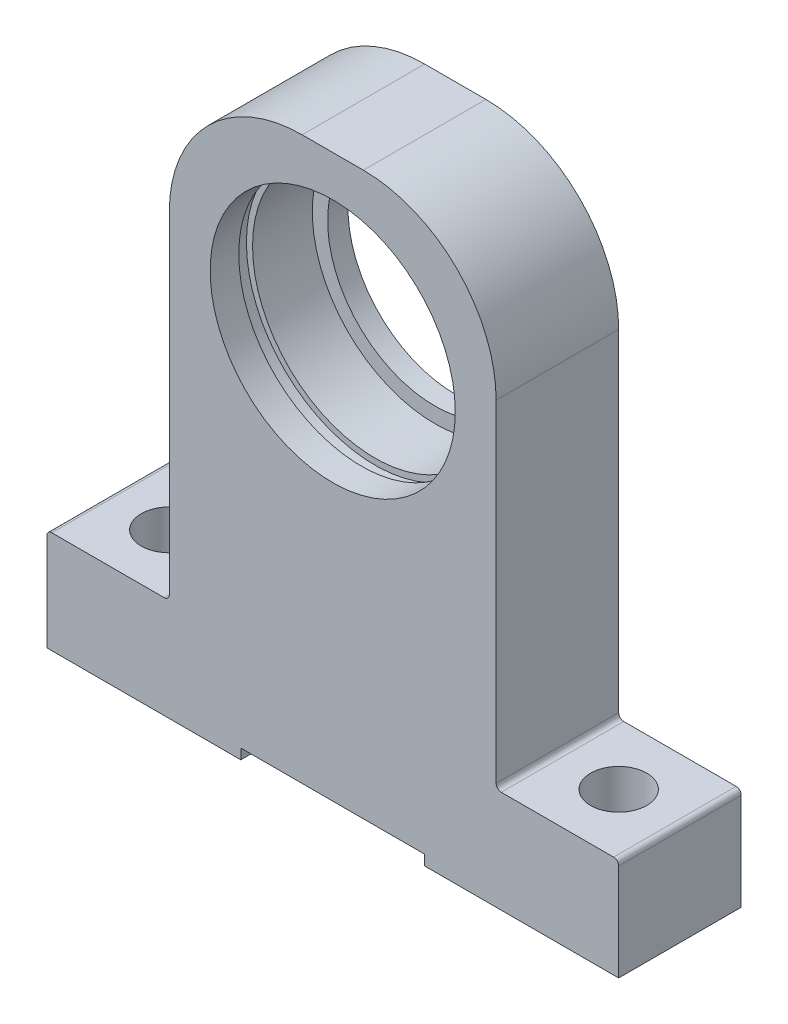
SolidWorks part; units mm, degrees
material "A6063"
ref_plane "Front Plane" through (0, 0, 0) normal (0, 0, 1) x (1, 0, 0)
ref_plane "Top Plane" through (0, 0, 0) normal (0, 1, 0) x (1, 0, 0)
ref_plane "Right Plane" through (0, 0, 0) normal (1, 0, 0) x (0, 0, -1)
ref_axis "Axis_X" through (-88.99, 0, 0) along (1, 0, 0)
ref_axis "Axis_Y" through (0, 55, 0) along (0, -1, 0)
ref_axis "Axis_Z" through (0, 0, -88.99) along (0, 0, 1)
sketch "Sketch1" plane through (0, 0, 0) normal (0, 0, 1) x (1, 0, 0)
  line L0 (-28, -40) -> (28, -40)
  line L1 (28, -40) -> (28, -30)
  line L2 (28, -30) -> (16, -30)
  line L3 (16, -30) -> (16, 16)
  line L4 (16, 16) -> (-16, 16)
  line L5 (-16, 16) -> (-16, -30)
  line L6 (-16, -30) -> (-28, -30)
  line L7 (-28, -30) -> (-28, -40)
  line L8 (0, 16) -> (0, -40) construction
  circle A0 centre (0, 0) radius 10.5
  dimension "DH_s" = 21
  dimension "S" = 10
  dimension "L" = 56
  dimension "L2" = 32
  dimension "H" = 56
  dimension "H_s" = 40
extrude "Boss-Extrude1" add sketch "Sketch1" along normal blind 12
sketch "Sketch2" plane through (0, 0, 0) normal (0, 0, 1) x (1, 0, 0)
  line L0 (3, 16) -> (16, 16)
  line L1 (16, 16) -> (16, 3)
  line L2 (-3, 16) -> (-16, 16)
  line L3 (-16, 16) -> (-16, 3)
  line L4 (16, 16) -> (-16, 16) construction
  line L5 (16, -30) -> (16, 16) construction
  line L7 (-16, 16) -> (-16, -30) construction
  arc A0 (3, 16) -> (16, 3) centre (3, 3) cw
  arc A1 (-16, 3) -> (-3, 16) centre (-3, 3) cw
  dimension "R" = 13
extrude "Cut-Extrude1" cut sketch "Sketch2" along normal through all
sketch "Sketch3" plane through (0, 0, 0) normal (0, 0, 1) x (1, 0, 0)
  line L0 (16, -29.5) -> (16, -30)
  line L1 (16, -30) -> (16, 16) construction
  line L2 (16, -30) -> (16.5, -30)
  line L3 (28, -30) -> (16, -30) construction
  line L4 (-16, -29.5) -> (-16, -30)
  line L5 (-16, 16) -> (-16, -30) construction
  line L6 (-16, -30) -> (-16.5, -30)
  line L7 (-16, -30) -> (-28, -30) construction
  arc A0 (16, -29.5) -> (16.5, -30) centre (16.5, -29.5) ccw
  arc A1 (-16.5, -30) -> (-16, -29.5) centre (-16.5, -29.5) ccw
  dimension "FIX_1" = 0.5
extrude "Boss-Extrude2" add sketch "Sketch3" along normal through all
sketch "Sketch4" plane through (0, 0, 0) normal (0, 0, 1) x (1, 0, 0)
  line L0 (-27.5, -30) -> (-28, -30)
  line L1 (-16, -30) -> (-28, -30) construction
  line L2 (-28, -30) -> (-28, -30.5)
  line L3 (-28, -30) -> (-28, -40) construction
  line L4 (27.5, -30) -> (28, -30)
  line L5 (28, -30) -> (16, -30) construction
  line L6 (28, -30) -> (28, -30.5)
  line L7 (28, -40) -> (28, -30) construction
  arc A0 (-28, -30.5) -> (-27.5, -30) centre (-27.5, -30.5) cw
  arc A1 (27.5, -30) -> (28, -30.5) centre (27.5, -30.5) cw
  dimension "FIX_2" = 0.5
extrude "Cut-Extrude2" cut sketch "Sketch4" along normal through all
sketch "Sketch5" plane through (0, -30, 0) normal (0, 1, 0) x (1, 0, 0)
  line L0 (0, 0) -> (0, -6) construction
  line L1 (-22, -6) -> (22, -6) construction
  line L2 (-16, 0) -> (-28, 0) construction
  circle A0 centre (-22, -6) radius 2.75
  circle A1 centre (22, -6) radius 2.75
  dimension "L1" = 44
  dimension "MSM_1" = 6
  dimension "D1_s" = 5.5
extrude "Cut-Extrude3" cut sketch "Sketch5" against normal through all
ref_plane "Plane1" through (0, 0, 12) normal (0, 0, 1) x (1, 0, 0)
sketch "Sketch7" plane through (0, 0, 12) normal (0, 0, 1) x (1, 0, 0)
  circle A0 centre (0, 0) radius 12
  dimension "D" = 24
extrude "Cut-Extrude4" cut sketch "Sketch7" against normal blind 10
sketch "Sketch10" plane through (0, 0, 12) normal (0, 0, 1) x (1, 0, 0)
  line L0 (-28, -40) -> (28, -40) construction
  line L1 (-9, -40) -> (9, -40)
  line L2 (-9, -40) -> (-9, -39)
  line L3 (-9, -39) -> (9, -39)
  line L4 (9, -40) -> (9, -39)
  line L5 (0, -39) -> (0, 0) construction
  dimension "D1" = 18
  dimension "MSM_4" = 1
extrude "Cut-Extrude5" cut sketch "Sketch10" against normal through all
sketch "Sketch11" plane through (0, 0, 0) normal (1, 0, 0) x (0, 0, -1)
  line L0 (0, 0) -> (-24.7164, 0) construction
  line L2 (-9.2, 12.6) -> (-7.85, 12.6)
  line L3 (-9.2, 12.6) -> (-9.2, 12)
  line L4 (-9.2, 12) -> (-7.85, 12)
  line L5 (-7.85, 12.6) -> (-7.85, 12)
  dimension "MSM_6" = 7.85
  dimension "MSM_7" = 1.35
  dimension "D" = 24
  dimension "MSM_5" = 25.2
revolve "Cut-Revolve1" cut sketch "Sketch11" angle 360 about axis through (0, 0, -88.99) along (0, 0, 1)
